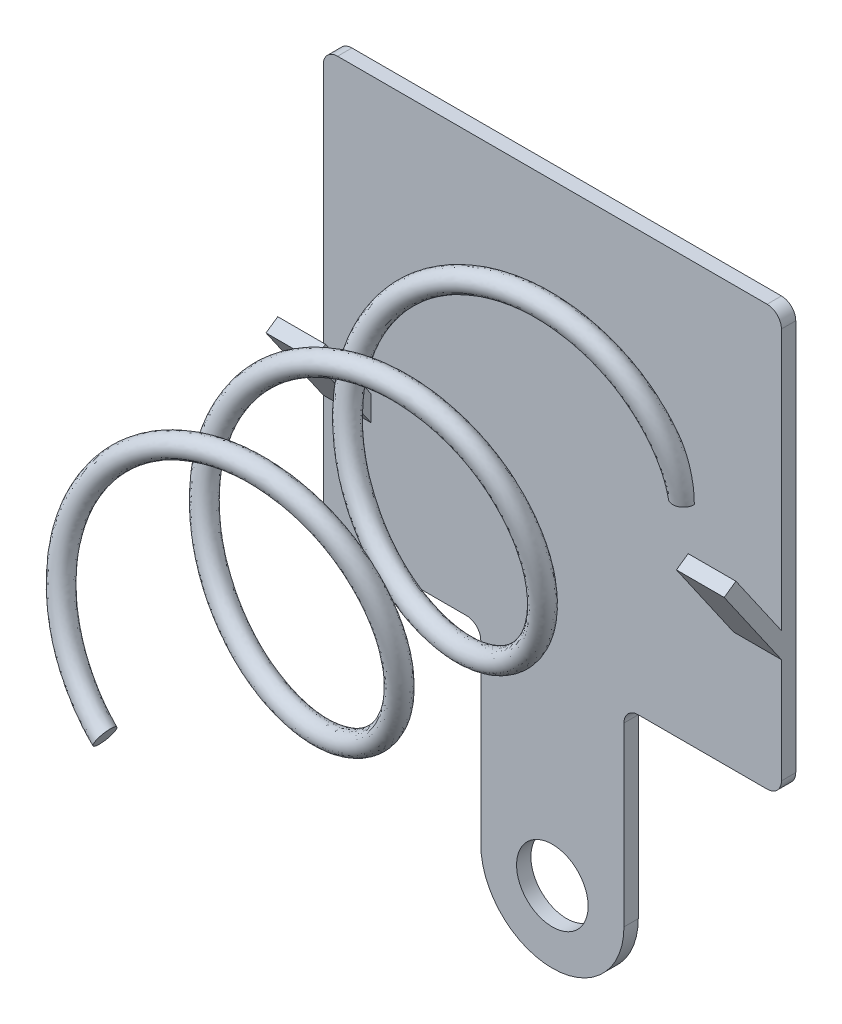
SolidWorks part; units mm, degrees
ref_plane "Front Plane" through (0, 0, 0) normal (0, 0, 1) x (1, 0, 0)
ref_plane "Top Plane" through (0, 0, 0) normal (0, 1, 0) x (1, 0, 0)
ref_plane "Right Plane" through (0, 0, 0) normal (1, 0, 0) x (0, 0, -1)
sketch "Sketch1" plane through (0, 0, 0) normal (0, 0, 1) x (1, 0, 0)
  line L0 (0, 0) -> (0, 4.4) construction
  line L1 (-4.8, 4.4) -> (4.8, 4.4)
  line L2 (4.8, 4.4) -> (4.8, -4.4)
  line L3 (4.8, -4.4) -> (1.5, -4.4)
  line L4 (1.5, -4.4) -> (1.5, -8.4)
  line L5 (0, 0) -> (0, -8.4) construction
  line L6 (-1.5, -4.4) -> (-1.5, -8.4)
  line L7 (-4.8, -4.4) -> (-1.5, -4.4)
  line L8 (-4.8, 4.4) -> (-4.8, -4.4)
  line L9 (-2.6852, -9.9) -> (3.5735, -9.9) construction
  line L10 (0, 0) -> (4.8, 0) construction
  arc A0 (1.5, -8.4) -> (-1.5, -8.4) centre (0, -8.4) cw
  circle A1 centre (0, -8.4) radius 0.75
  dimension "D5" = 1.5
  dimension "D1" = 9.6
  dimension "D2" = 8.8
  dimension "D3" = 14.3
  dimension "D4" = 3
extrude "Boss-Extrude1" add sketch "Sketch1" along normal blind 0.3
fillet "Fillet1" radius 0.3 6 edges at (-1.5, -4.4, 0.15) (1.5, -4.4, 0.15) (4.8, -4.4, 0.15) (-4.8, -4.4, 0.15) (-4.8, 4.4, 0.15) (4.8, 4.4, 0.15)
sketch "Sketch2" plane through (4.8, 0, 0) normal (1, 0, 0) x (0, 0, -1)
  line L0 (-0.3, -1.9) -> (-1.5, -0.1711)
  line L1 (-0.3, -4.1) -> (-0.3, 4.1) construction
  line L2 (-1.5, -0.1711) -> (-1.2535, 0)
  line L3 (-1.2535, 0) -> (-0.3, -1.3739)
  line L4 (-0.3, -1.3739) -> (-0.3, -1.9)
  line L5 (-0.3, 4.4) -> (0, 4.4) construction
  line L6 (0, -4.1) -> (0, 4.1) construction
  line L7 (0, -4.4) -> (-0.3, -4.4) construction
  dimension "D1" = 0.3
  dimension "D2" = 6.3
  dimension "D3" = 1.5
  dimension "D4" = 4.4
extrude "Boss-Extrude2" add sketch "Sketch2" against normal blind 1
mirror "Mirror1" about plane through (0, 0, 0) normal (1, 0, 0) of "Boss-Extrude2"
sketch "Sketch3" plane through (0, 0, 0.3) normal (0, 0, 1) x (1, 0, 0)
  circle A0 centre (0, 0) radius 2.75
  point P2 (0, 0.136)
  point P3 (0, 0)
  dimension "D1" = 5.5
curve "Helix/Spiral1" pitch 3 height 8 radius 2.75 centre (0, 0, 0.3) axis (0, 0, 1) start towards (1, 0, 0)
sketch "Sketch4" plane through (0, 0, 0) normal (0, 1, 0) x (1, 0, 0)
  line L0 (4.5, -0.3) -> (-4.5, -0.3) construction
  circle A0 centre (2.75, -0.3) radius 0.225
  spline S0 degree 3 poles (2.75, -0.3) (2.75, -0.3631) (2.6022, -0.4907) (1.9718, -0.6809) (1.0317, -0.8714) (-0.0704, -1.0619) (-1.1614, -1.2524) (-2.0701, -1.4429) (-2.6536, -1.6333) (-2.8204, -1.8238) (-2.5443, -2.0143) (-1.8685, -2.2048) (-0.8994, -2.3952) (0.211, -2.5857) (1.2883, -2.7762) (2.1632, -2.9667) (2.6985, -3.1571) (2.8099, -3.3476) (2.48, -3.5381) (1.7607, -3.7286) (0.7648, -3.919) (-0.3511, -4.1095) (-1.412, -4.3) (-2.251, -4.4905) (-2.7366, -4.681) (-2.7924, -4.8714) (-2.4096, -5.0619) (-1.6484, -5.2524) (-0.6284, -5.4429) (0.4904, -5.6333) (1.5321, -5.8238) (2.3332, -6.0143) (2.7679, -6.2048) (2.7679, -6.3952) (2.3332, -6.5857) (1.5321, -6.7762) (0.4904, -6.9667) (-0.6284, -7.1571) (-1.6484, -7.3476) (-2.4096, -7.5381) (-2.7924, -7.7286) (-2.7363, -7.9191) (-2.252, -8.1093) (-1.6897, -8.2369) (-1.375, -8.3) knots 0 0 0 0 0.02381 0.047619 0.071429 0.095238 0.119048 0.142857 0.166667 0.190476 0.214286 0.238095 0.261905 0.285714 0.309524 0.333333 0.357143 0.380952 0.404762 0.428571 0.452381 0.47619 0.5 0.52381 0.547619 0.571429 0.595238 0.619048 0.642857 0.666667 0.690476 0.714286 0.738095 0.761905 0.785714 0.809524 0.833333 0.857143 0.880952 0.904762 0.928571 0.952381 0.97619 1 1 1 1 construction
  point P2 (2.75, -0.3)
  dimension "D1" = 0.45
sweep "Sweep1" add profiles "Sketch4" path "Helix/Spiral1"
